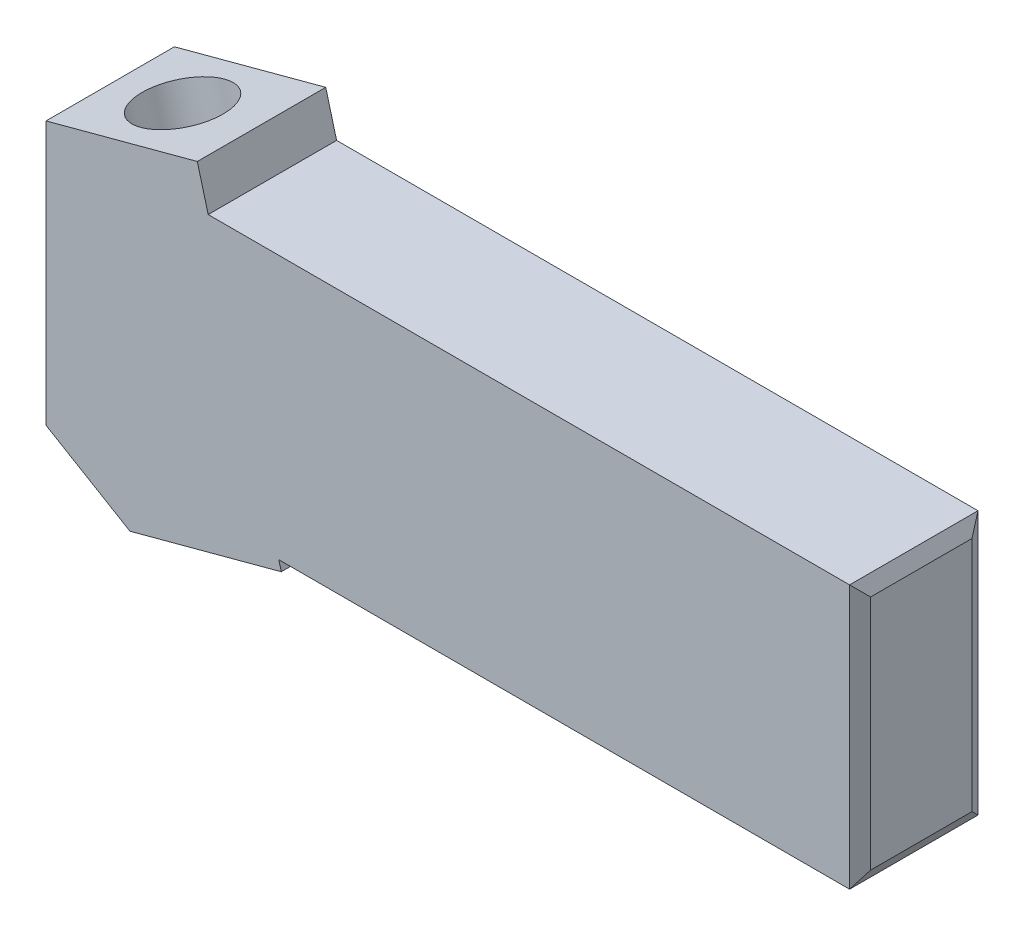
SolidWorks part; units mm, degrees
ref_plane "Front Plane" through (0, 0, 0) normal (0, 0, 1) x (1, 0, 0)
ref_plane "Top Plane" through (0, 0, 0) normal (0, 1, 0) x (1, 0, 0)
ref_plane "Right Plane" through (0, 0, 0) normal (1, 0, 0) x (0, 0, -1)
sketch "Sketch1" plane through (0, 0, 0) normal (0, 1, 0) x (1, 0, 0)
  line L1 (0, 0) -> (60, 0)
  line L2 (0, 0) -> (0, 9.5)
  line L3 (0, 9.5) -> (60, 9.5)
  line L4 (60, 0) -> (60, 9.5)
extrude "Boss-Extrude1" add sketch "Sketch1" along normal blind 9.5
sketch3d "3DSketch1" plane through (0, 0, 0) normal (0, 0, 1) x (1, 0, 0)
  dimension "D1" = 15
sketch "Sketch4" plane through (-2.375, 8.8636, 0) normal (-0.2588, 0.9659, 0) x (0.9659, 0.2588, 0)
  line L1 (2.4588, 0) -> (14.0478, 0)
  line L2 (2.4588, 0) -> (2.4588, 9.5)
  line L3 (2.4588, 9.5) -> (14.0478, 9.5)
  line L4 (14.0478, 0) -> (14.0478, 9.5)
extrude "Boss-Extrude2" add sketch "Sketch4" against normal blind 24 contours L2 L1 L4 L3
extrude "Boss-Extrude3" add sketch "Sketch1<2>" against normal blind 10
sketch "Sketch1<2>" plane through (0, 0, 0) normal (0, 1, 0) x (1, 0, 0) same geometry as "Sketch1"
sketch "Sketch7" plane through (-2.375, 8.8636, 0) normal (-0.2588, 0.9659, 0) x (0.9659, 0.2588, 0)
  circle A0 centre (8, 4.75) radius 3.1
extrude "Cut-Extrude2" cut sketch "Sketch7" against normal through all contours A0
sketch "Sketch13" plane through (0, 0, -9.5) normal (0, 0, -1) x (-1, 0, 0)
  line L0 (-6.2117, -13.6822) -> (0, -10)
  line L1 (0, -10) -> (-5.225, -10)
  line L2 (-5.225, -10) -> (-6.2117, -13.6822)
extrude "Boss-Extrude7" add sketch "Sketch13" against normal blind 9.5
chamfer "Chamfer1" distance 1 angle 29 4 edges at (60, 9.5, -4.75) (60, -0.25, 0) (60, -10, -4.75) (60, -0.25, -9.5) first distance on face at (60, -0.25, -4.75)
